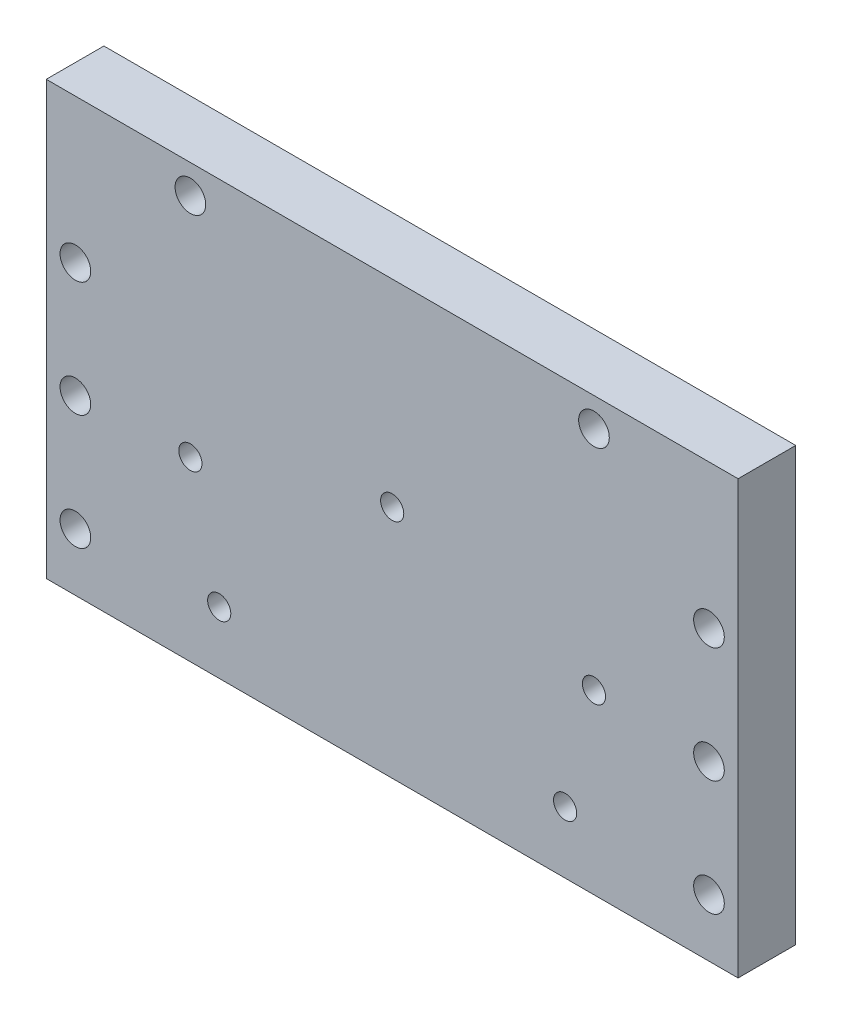
SolidWorks part; units mm, degrees
ref_plane "Front Plane" through (0, 0, 0) normal (0, 0, 1) x (1, 0, 0)
ref_plane "Top Plane" through (0, 0, 0) normal (0, 1, 0) x (1, 0, 0)
ref_plane "Right Plane" through (0, 0, 0) normal (1, 0, 0) x (0, 0, -1)
sketch "Sketch1" plane through (0, 0, 0) normal (0, 0, 1) x (1, 0, 0)
  line L11 (-76.2, 47.625) -> (76.2, 47.625)
  line L12 (-76.2, 47.625) -> (-76.2, -47.625)
  line L13 (-76.2, -47.625) -> (76.2, -47.625)
  line L14 (76.2, 47.625) -> (76.2, -47.625)
  line L15 (-76.2, 47.625) -> (76.2, -47.625) construction
  line L16 (-76.2, -47.625) -> (76.2, 47.625) construction
  point P0 (0, 0)
  dimension "D1" = 152.4
  dimension "D2" = 95.25
extrude "Boss-Extrude1" add sketch "Sketch1" along normal mid plane 12.7
hole_wizard "1/4 Clearance Hole1" positions "Sketch2" profile "Sketch3" hole size "1/4" standard "ANSI Inch" end condition through all
sketch "Sketch2" plane through (0, 0, 6.35) normal (0, 0, 1) x (1, 0, 0)
  line L0 (-44.45, 41.275) -> (44.45, 41.275)
  line L3 (76.2, 47.625) -> (-76.2, 47.625) construction
  point P0 (-44.45, 41.275)
  point P2 (44.45, 41.275)
  point P9 (0, 41.275)
  point P15 (69.7851, 15.875)
  point P18 (69.7851, -9.525)
  point P21 (69.7851, -34.925)
  point P24 (-69.7851, 15.875)
  point P27 (-69.7851, -9.525)
  point P34 (-69.7851, -34.925)
  dimension "D1" = 6.35
  dimension "D2" = 88.9
sketch "Sketch3" plane through (-44.45, 41.275, 6.35) normal (1, 0, 0) x (0, -1, 0)
  line L0 (0, 0) -> (0, 12.7)
  line L1 (0, 12.7) -> (3.3782, 12.7)
  line L2 (3.3782, 12.7) -> (3.3782, 0)
  line L5 (3.3782, 0) -> (0, 0)
  line L11 (0, -6.35) -> (0, 107.95) construction
  dimension "Thru Hole Dia." = 6.7564
  dimension "Thru Hole Depth" = 12.7
hole_wizard "Tap Drill for 1/4-20 Tap1" positions "Sketch4" profile "Sketch5" hole size "1/4-20" standard "ANSI Inch" end condition through all
sketch "Sketch4" plane through (0, 0, 6.35) normal (0, 0, 1) x (1, 0, 0)
  line L0 (-44.45, -8.5852) -> (44.45, -8.5852)
  line L2 (38.1, -33.9852) -> (-38.1, -33.9852)
  line L4 (-76.2, -47.625) -> (76.2, -47.625) construction
  point P0 (-38.1, -33.9852)
  point P2 (38.1, -33.9852)
  point P4 (-44.45, -8.5852)
  point P6 (44.45, -8.5852)
  point P8 (0, 4.1148)
  point P27 (0, -8.5852)
  point P28 (0, -33.9852)
  dimension "D1" = 13.6398
  dimension "D2" = 76.2
  dimension "D3" = 88.9
  dimension "D4" = 25.4
  dimension "D5" = 12.7
sketch "Sketch5" plane through (-38.1, -33.9852, 6.35) normal (1, 0, 0) x (0, -1, 0)
  line L0 (0, 0) -> (0, 12.7)
  line L1 (0, 12.7) -> (2.5527, 12.7)
  line L2 (2.5527, 12.7) -> (2.5527, 0)
  line L5 (2.5527, 0) -> (0, 0)
  line L11 (0, -6.35) -> (0, 107.95) construction
  dimension "Thru Hole Dia." = 5.1054
  dimension "Thru Hole Depth" = 12.7
